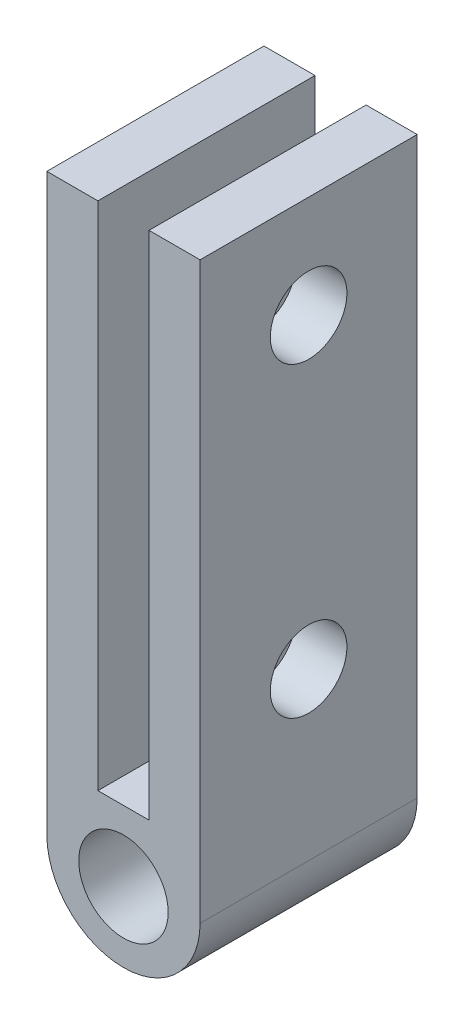
SolidWorks part; units mm, degrees
ref_plane "Alzado" through (0, 0, 0) normal (0, 0, 1) x (1, 0, 0)
ref_plane "Planta" through (0, 0, 0) normal (0, 1, 0) x (1, 0, 0)
ref_plane "Vista lateral" through (0, 0, 0) normal (1, 0, 0) x (0, 0, -1)
sketch "Croquis1" plane through (0, 0, 0) normal (0, 0, 1) x (1, 0, 0)
  line L0 (1, 0) -> (-1, 0)
  line L1 (-1, 0) -> (-1, 20)
  line L2 (-1, 20) -> (-3, 20)
  line L3 (-3, 20) -> (-3, -5.5)
  line L4 (-3, -5.5) -> (3, -5.5)
  line L5 (0, 0) -> (0, -5.5) construction
  line L6 (3, 20) -> (3, -5.5)
  line L7 (1, 20) -> (3, 20)
  line L8 (1, 0) -> (1, 20)
  circle A0 centre (0, -2.75) radius 1.75
  dimension "D5" = 3.5
  dimension "D1" = 1
  dimension "D2" = 20
  dimension "D3" = 2
  dimension "D4" = 5.5
extrude "Saliente-Extruir1" add sketch "Croquis1" along normal blind 8.5
fillet "Redondeo1" radius 3 2 edges at (-3, -5.5, 4.25) (3, -5.5, 4.25)
sketch "Croquis2" plane through (3, 0, 0) normal (1, 0, 0) x (0, 0, -1)
  line L0 (-8.5, 20) -> (0, 20) construction
  circle A0 centre (-4.25, 16) radius 1.5
  circle A1 centre (-4.25, 4) radius 1.5
  dimension "D1" = 3
  dimension "D3" = 3
  dimension "D2" = 4
  dimension "D4" = 12
extrude "Cortar-Extruir1" cut sketch "Croquis2" against normal up to vertex (6 mm away) up to point (-3, -2.5, 8.5)
